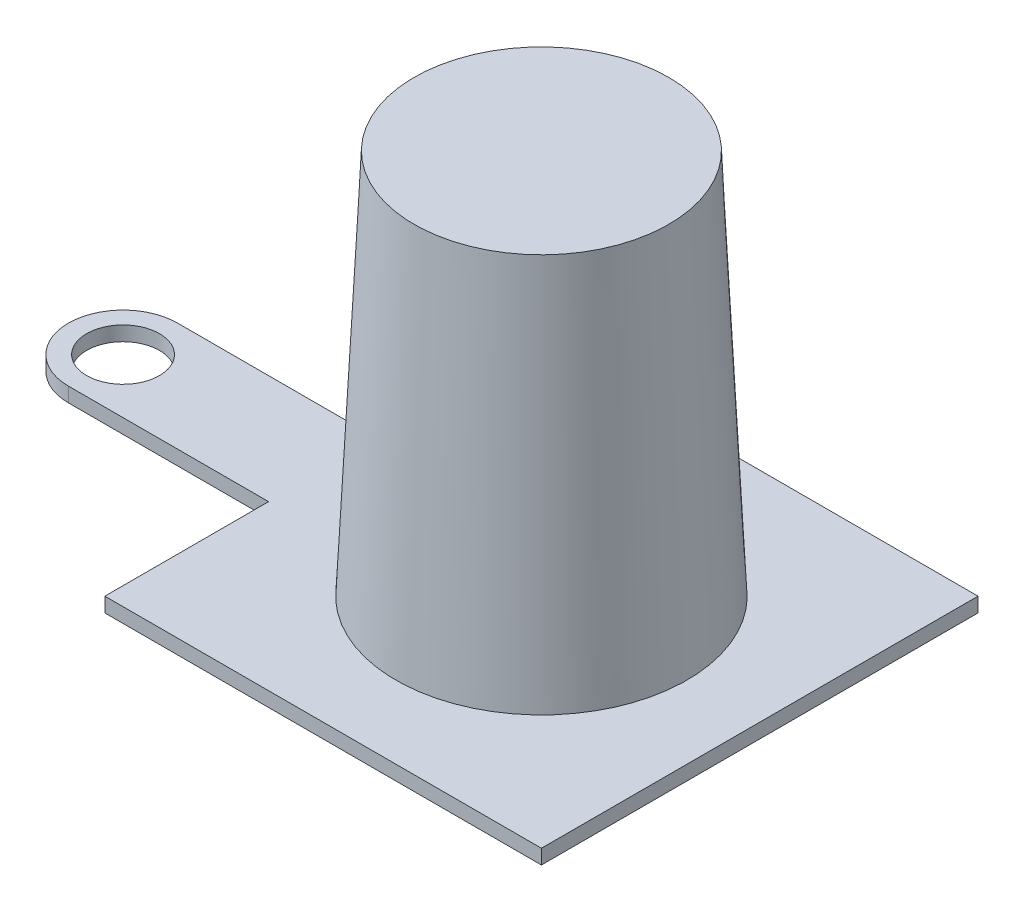
SolidWorks part; units mm, degrees
ref_plane "前视基准面" through (0, 0, 0) normal (0, 0, 1) x (1, 0, 0)
ref_plane "上视基准面" through (0, 0, 0) normal (0, 1, 0) x (1, 0, 0)
ref_plane "右视基准面" through (0, 0, 0) normal (1, 0, 0) x (0, 0, -1)
other "Configuration Table"
sketch "草图1" plane through (0, 0, 0) normal (0, 1, 0) x (1, 0, 0)
  line L1 (-6, -6) -> (6, -6)
  line L2 (-6, -6) -> (-6, 6)
  line L3 (-6, 6) -> (6, 6)
  line L4 (6, -6) -> (6, 6)
  line L5 (-6, -6) -> (6, 6) construction
  line L6 (-6, 6) -> (6, -6) construction
  line L7 (-6, 1.5) -> (-13, 1.5)
  line L8 (-6, 1.5) -> (-6, -1.5)
  line L9 (-6, -1.5) -> (-13, -1.5)
  line L10 (-13, 1.5) -> (-13, -1.5)
  circle A0 centre (0, 0) radius 4
  circle A1 centre (0, 0) radius 3.5
  circle A2 centre (-11.5, 0) radius 1
  point P12 (-13, 0)
  dimension "D1" = 8
  dimension "D2" = 7
  dimension "D7" = 2
  dimension "D3" = 12
  dimension "D4" = 3
  dimension "D5" = 7
  dimension "D6" = 1.5
extrude "凸台-拉伸1" add sketch "草图1" along normal blind 0.4 contours L1 L4 L3 L2 | L7 L10 L9 L8 | A2
extrude "凸台-拉伸2" add sketch "草图1<5>" along normal blind 10.6 from surface contours A1 starting at face at (-4.75, 0.4, 0)
sketch "草图1<5>" plane through (0, 0, 0) normal (0, 1, 0) x (1, 0, 0) same geometry as "草图1"
extrude "凸台-拉伸3" add sketch "草图1<6>" along normal blind 0.01 from surface contours A0 starting at face at (0, 0.4, -3.5)
sketch "草图1<6>" plane through (0, 0, 0) normal (0, 1, 0) x (1, 0, 0) same geometry as "草图1"
loft "放样1" add section edge at (0, 11, -3.5) section edge at (0, 0.4, -4)
fillet "圆角1" radius 1.5 2 edges at (-13, 0.2, 1.5) (-13, 0.2, -1.5)
